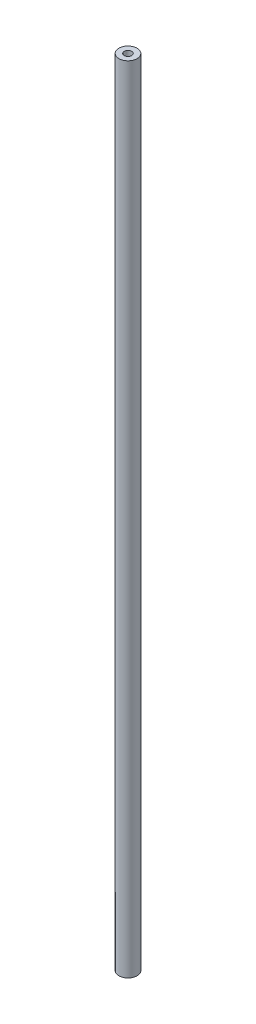
SolidWorks part; units mm, degrees
ref_plane "Front Plane" through (0, 0, 0) normal (0, 0, 1) x (1, 0, 0)
ref_plane "Top Plane" through (0, 0, 0) normal (0, 1, 0) x (1, 0, 0)
ref_plane "Right Plane" through (0, 0, 0) normal (1, 0, 0) x (0, 0, -1)
sketch "Sketch3" plane through (0, 0, 0) normal (0, 1, 0) x (1, 0, 0)
  circle A0 centre (0, 0) radius 4
  dimension "D1" = 8
extrude "Boss-Extrude1" add sketch "Sketch3" along normal blind 350
hole_wizard "M4 Tapped Hole1" positions "Sketch5" profile "Sketch4" tap size "M4" standard "ISO"
sketch "Sketch5" plane through (0, 350, 0) normal (0, 1, 0) x (1, 0, 0)
  point P0 (0, 0)
sketch "Sketch4" plane through (0, 350, 0) normal (1, 0, 0) x (0, 0, 1)
  line L0 (0, 0) -> (0, 3.3914)
  line L1 (0, 3.3914) -> (1.65, 2.4)
  line L2 (1.65, 2.4) -> (1.65, 0)
  line L5 (1.65, 0) -> (0, 0)
  line L10 (0, 3.3914) -> (-1.65, 2.4) construction
  line L11 (0, -6.35) -> (0, 107.95) construction
  dimension "Tap Drill Dia." = 3.3
  dimension "Tap Drill Depth" = 2.4
  dimension "Drill Angle" = 118
cosmetic thread "Hole Thread1" parameters "D1"=2.4, "D2"=4
hole_wizard "M4 Tapped Hole2" positions "Sketch7" profile "Sketch6" tap size "M4" standard "ISO"
sketch "Sketch7" plane through (0, 0, 0) normal (0, -1, 0) x (-1, 0, 0)
  point P0 (0, 0)
sketch "Sketch6" plane through (0, 0, 0) normal (1, 0, 0) x (0, 0, -1)
  line L0 (0, 0) -> (0, 3.3914)
  line L1 (0, 3.3914) -> (1.65, 2.4)
  line L2 (1.65, 2.4) -> (1.65, 0)
  line L5 (1.65, 0) -> (0, 0)
  line L10 (0, 3.3914) -> (-1.65, 2.4) construction
  line L11 (0, -6.35) -> (0, 107.95) construction
  dimension "Tap Drill Dia." = 3.3
  dimension "Tap Drill Depth" = 2.4
  dimension "Drill Angle" = 118
cosmetic thread "Hole Thread2"
